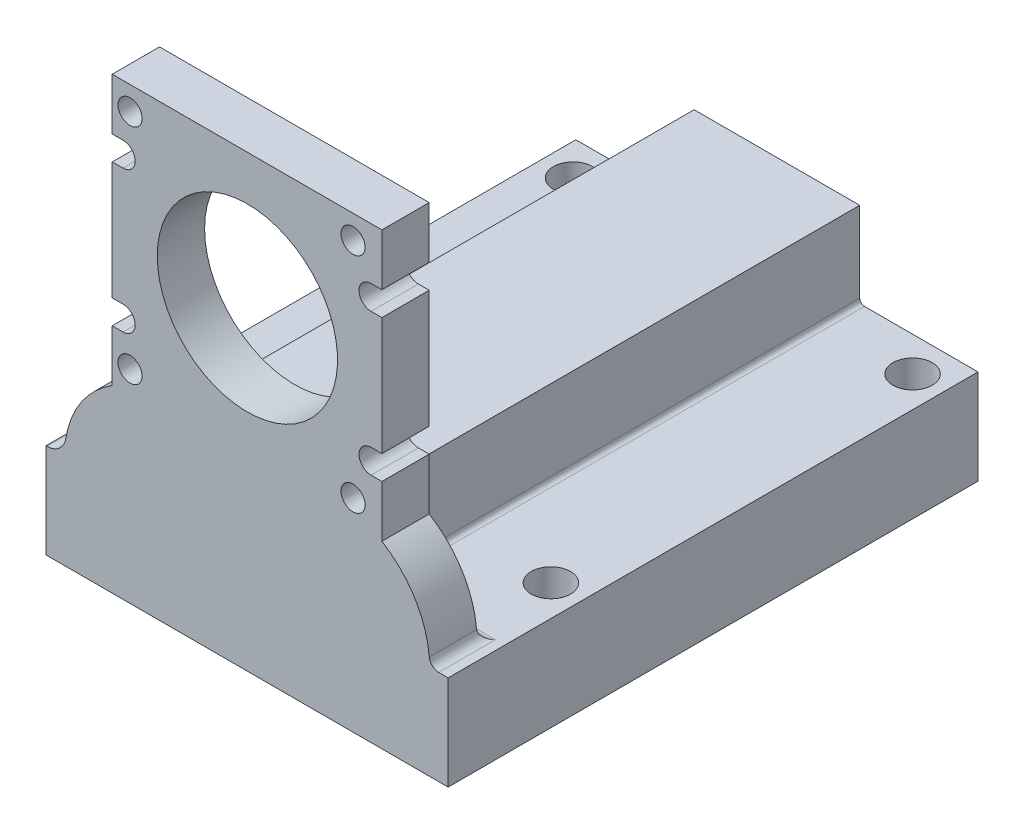
SolidWorks part; units mm, degrees
ref_plane "Front Plane" through (0, 0, 0) normal (0, 0, 1) x (1, 0, 0)
ref_plane "Top Plane" through (0, 0, 0) normal (0, 1, 0) x (1, 0, 0)
ref_plane "Right Plane" through (0, 0, 0) normal (1, 0, 0) x (0, 0, -1)
sketch "Sketch3" plane through (0, 0, 0) normal (0, 0, 1) x (1, 0, 0)
  line L0 (26.2106, 17.55) -> (28.5, 17.55)
  line L1 (-28.5, -28.5) -> (28.5, -28.5)
  line L2 (-28.5, -28.5) -> (-28.5, 28.5)
  line L3 (-28.5, 28.5) -> (28.5, 28.5)
  line L4 (28.5, -28.5) -> (28.5, 28.5)
  line L5 (-28.5, -28.5) -> (28.5, 28.5) construction
  line L6 (-28.5, 28.5) -> (28.5, -28.5) construction
  line L7 (26.2106, 12.45) -> (28.5, 12.45)
  line L8 (26.2106, -12.45) -> (28.5, -12.45)
  line L9 (26.2106, -17.55) -> (28.5, -17.55)
  line L10 (28.5, -12.45) -> (28.5, -17.55)
  line L11 (28.5, 17.55) -> (28.5, 12.45)
  line L12 (0, -31.8008) -> (0, 23.7973) construction
  line L13 (-26.2106, -12.45) -> (-28.5, -12.45)
  line L14 (-28.5, -12.45) -> (-28.5, -17.55)
  line L15 (-26.2106, -17.55) -> (-28.5, -17.55)
  line L16 (-26.2106, 17.55) -> (-28.5, 17.55)
  line L17 (-26.2106, 12.45) -> (-28.5, 12.45)
  line L18 (-28.5, 17.55) -> (-28.5, 12.45)
  line L19 (0, 0) -> (35.3565, 0) construction
  line L20 (-1.1674, -0.0491) -> (27.3326, -0.0491) construction
  line L21 (-17.5, -28.5) -> (17.5, -28.5)
  line L22 (17.5, -28.5) -> (17.5, -46.5)
  line L23 (17.5, -46.5) -> (42.5, -46.5)
  line L24 (42.5, -46.5) -> (42.5, -66.5)
  line L25 (42.5, -66.5) -> (-42.5, -66.5)
  line L26 (-42.5, -66.5) -> (-42.5, -46.5)
  line L27 (-42.5, -46.5) -> (-17.5, -46.5)
  line L28 (-17.5, -46.5) -> (-17.5, -28.5)
  arc A0 (26.2106, 17.55) -> (26.2106, 12.45) centre (26.2106, 15) ccw
  arc A1 (26.2106, -12.45) -> (26.2106, -17.55) centre (26.2106, -15) ccw
  arc A2 (-26.2106, -12.45) -> (-26.2106, -17.55) centre (-26.2106, -15) cw
  arc A3 (-26.2106, 17.55) -> (-26.2106, 12.45) centre (-26.2106, 15) cw
  circle A4 centre (-24.7374, 23.5209) radius 2.55
  circle A5 centre (22.4026, 23.5209) radius 2.55
  circle A6 centre (22.4026, -23.6191) radius 2.55
  circle A7 centre (-24.7374, -23.6191) radius 2.55
  circle A8 centre (-0.6372, -0.445) radius 19.05
  circle A9 centre (-0.1094, -0.3131) radius 5.25
  circle A10 centre (-0.1094, -0.3131) radius 6
  point P0 (0, 0)
  point P56 (0, -28.5)
  dimension "D3" = 5.1
  dimension "D8" = 5.1
  dimension "D9" = 12
  dimension "D1" = 57
  dimension "D2" = 57
  dimension "D4" = 12.45
  dimension "D5" = 15
  dimension "D6" = 5.1
  dimension "D7" = 47.14
  dimension "D10" = 35
  dimension "D11" = 18
  dimension "D12" = 18
  dimension "D13" = 20
  dimension "D14" = 25
  dimension "D15" = 25
extrude "Boss-Extrude1" add sketch "Sketch3" against normal blind 10 contours L2 L1 L4 L3
extrude "Cut-Extrude1" cut sketch "Sketch3<3>" against normal blind 10 contours A4 | A5 | A3 L17 L18 L16 | A0 L7 L11 L0 | A2 L15 L14 L13 | L9 L10 L8 A1 | A7 | A6
sketch "Sketch3<3>" plane through (0, 0, 0) normal (0, 0, 1) x (1, 0, 0) same geometry as "Sketch3"
extrude "Boss-Extrude2" add sketch "Sketch3<4>" against normal blind 112 contours L28 L27 L26 L25 L24 L23 L22 L1 region at (0, -51.3627, 0)
sketch "Sketch3<4>" plane through (0, 0, 0) normal (0, 0, 1) x (1, 0, 0) same geometry as "Sketch3"
sketch "Sketch4" plane through (0, 0, -10) normal (0, 0, -1) x (-1, 0, 0)
  circle A0 centre (-0.0709, -0.0077) radius 19.05
  circle A1 centre (-0.0709, -0.0077) radius 6.5
  dimension "D1" = 13
extrude "Cut-Extrude2" cut sketch "Sketch4" against normal through all contours A1 | A0 A1 | A0 region at (18.5821, -0.0077, -10) region at (0.0709, -0.0077, -10)
sketch "Sketch5" plane through (0, -46.5, 0) normal (0, 1, 0) x (1, 0, 0)
  circle A0 centre (35.9556, 104.7113) radius 4.15
  circle A1 centre (35.9556, 28.2619) radius 4.15
  circle A2 centre (-35.8216, 28.2619) radius 4.15
  circle A3 centre (-35.8216, 104.7113) radius 4.15
  point P8 (-35.8216, 104.7113)
  point P9 (35.9556, 104.7113)
  point P10 (35.9556, 11.1519)
  point P11 (-35.8216, 11.1519)
  point P12 (-35.8216, 28.2619)
  point P13 (35.9556, 28.2619)
  dimension "D1" = 8.3
extrude "Cut-Extrude5" cut sketch "Sketch5" against normal through all
sketch "Sketch6" plane through (0, 0, 0) normal (0, 0, 1) x (1, 0, 0)
  line L0 (-42.5, -46.5) -> (-17.5, -46.5) construction
  line L1 (0, 0) -> (0, -66.5) construction
  line L2 (42.5, -66.5) -> (-42.5, -66.5) construction
  line L3 (-28.5, -28.5) -> (-17.5, -46.5)
  line L4 (-17.5, -46.5) -> (-17.5, -28.5)
  line L5 (-17.5, -28.5) -> (-28.5, -28.5)
  line L6 (-17.5, -46.5) -> (-38.595, -46.5)
  line L7 (28.5, -28.5) -> (17.5, -28.5)
  line L8 (17.5, -28.5) -> (17.5, -46.5)
  line L9 (17.5, -46.5) -> (28.5, -28.5)
  line L10 (38.595, -46.5) -> (17.5, -46.5)
  arc A0 (-28.5, -28.5) -> (-38.595, -46.5) centre (-17.5, -46.5) ccw
  arc A1 (28.5, -28.5) -> (38.595, -46.5) centre (17.5, -46.5) cw
  line M7 (-28.5, -28.5) -> (-17.5, -28.5)
  line M8 (-17.5, -28.5) -> (-17.5, -46.5)
  line M9 (-17.5, -46.5) -> (-42.5, -46.5)
  line M13 (42.5, -46.5) -> (17.5, -46.5)
  line M14 (17.5, -46.5) -> (17.5, -28.5)
  line M15 (17.5, -28.5) -> (28.5, -28.5)
extrude "Boss-Extrude3" add sketch "Sketch6" against normal blind 10 contours L3 A0 M9 | L3 M7 M8 | A1 L9 M13 | L9 M14 M15 region at (-21.1667, -34.5, 0) region at (-29.2388, -39.9164, 0) region at (21.1667, -34.5, 0) region at (29.2388, -39.9164, 0)
fillet "Fillet2" radius 4 2 edges at (-28.0475, -46.5, -10) (-38.595, -46.5, -5) type face fillet first side face at (35.9556, -46.5, -100.5613) first side face at (-18.9791, -0.0077, -10) first side face at (-34.7232, -36.8406, -5) second side face at (-35.8216, -46.5, -100.5613)
fillet "Fillet3" radius 2 2 edges at (38.595, -46.5, -5) (28.0475, -46.5, -10) type face fillet first side face at (34.7232, -36.8406, -5) first side face at (-18.9791, -0.0077, -10) second side face at (35.9556, -46.5, -100.5613)
fillet "Fillet4" radius 1 3 edges at (-17.5, -35.5, -10) (17.5, -36.5, -10) (0, -28.5, -10) type face fillet first side face at (-18.9791, -0.0077, -10) second side face at (-17.5, -38.6657, -51.4343) second side face at (17.5, -38.9828, -51.1172) second side face at (0, -28.5, -61)
